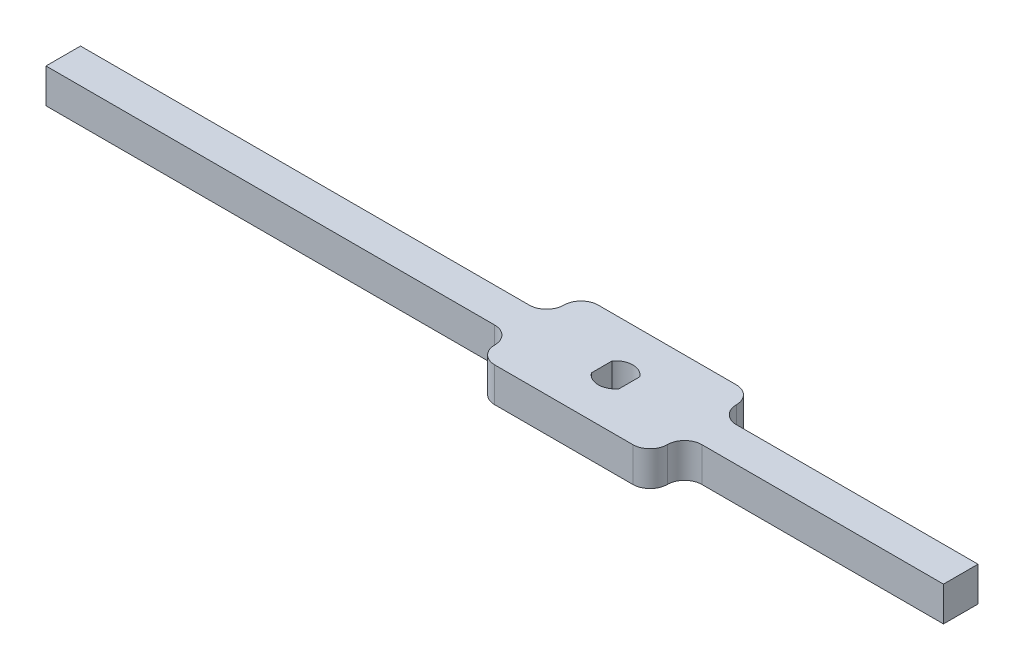
SolidWorks part; units mm, degrees
ref_plane "Front Plane" through (0, 0, 0) normal (0, 0, 1) x (1, 0, 0)
ref_plane "Top Plane" through (0, 0, 0) normal (0, 1, 0) x (1, 0, 0)
ref_plane "Right Plane" through (0, 0, 0) normal (1, 0, 0) x (0, 0, -1)
sketch "Sketch1" plane through (0, 0, 0) normal (0, 1, 0) x (1, 0, 0)
  line L0 (-4, 3) -> (-4, -3)
  line L1 (0, 5) -> (0, -5) construction
  line L2 (4, 3) -> (4, -3)
  line L4 (-25, -15) -> (25, -15)
  line L5 (-25, -15) -> (-25, 15)
  line L6 (-25, 15) -> (25, 15)
  line L7 (25, -15) -> (25, 15)
  line L8 (-25, -15) -> (25, 15) construction
  line L9 (-25, 15) -> (25, -15) construction
  arc A0 (-4, -3) -> (4, -3) centre (0, 0) ccw
  arc A1 (4, 3) -> (-4, 3) centre (0, 0) ccw
  dimension "D1" = 10
  dimension "D2" = 4
  dimension "D3" = 50
  dimension "D4" = 30
extrude "Boss-Extrude1" add sketch "Sketch1" along normal blind 10
sketch "Sketch2" plane through (0, 0, 0) normal (0, -1, 0) x (1, 0, 0)
  line L0 (-25, 5) -> (-160, 5)
  line L1 (-25, -15) -> (-25, 15) construction
  line L2 (-160, 5) -> (-160, -5)
  line L3 (-160, -5) -> (-25, -5)
  line L4 (25, 5) -> (100, 5)
  line L5 (25, 15) -> (25, -15) construction
  line L6 (100, 5) -> (100, -5)
  line L7 (100, -5) -> (25, -5)
  line L10 (-25, 5) -> (-25, -5)
  line L11 (25, 5) -> (25, -5)
  dimension "D1" = 5
  dimension "D2" = 10
  dimension "D3" = 10
  dimension "D4" = 160
  dimension "D5" = 100
extrude "Boss-Extrude3" add sketch "Sketch2" against normal up to surface (10 mm away) up to face at (0, 10, 0)
fillet "Fillet1" radius 5 4 edges at (-25, 5, 5) (-25, 5, -5) (25, 5, -5) (25, 5, 5)
fillet "Fillet2" radius 5 4 edges at (25, 5, 15) (-25, 5, 15) (-25, 5, -15) (25, 5, -15)
